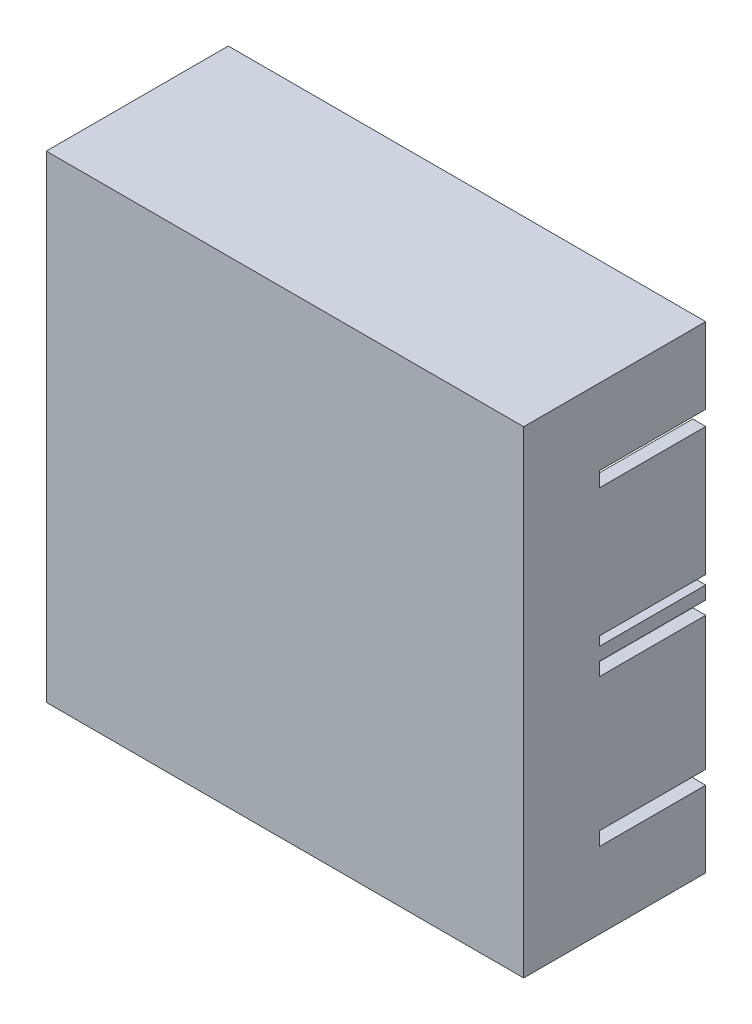
SolidWorks part; units mm, degrees
ref_plane "Front Plane" through (0, 0, 0) normal (0, 0, 1) x (1, 0, 0)
ref_plane "Top Plane" through (0, 0, 0) normal (0, 1, 0) x (1, 0, 0)
ref_plane "Right Plane" through (0, 0, 0) normal (1, 0, 0) x (0, 0, -1)
sketch "Sketch1" plane through (0, 0, 0) normal (0, 0, 1) x (1, 0, 0)
  line L1 (24.5589, 1.4668) -> (46.5589, 1.4668)
  line L2 (24.5589, 1.4668) -> (24.5589, -20.5332)
  line L3 (24.5589, -20.5332) -> (46.5589, -20.5332)
  line L4 (46.5589, 1.4668) -> (46.5589, -20.5332)
  dimension "D1" = 22
  dimension "D2" = 22
extrude "Boss-Extrude1" add sketch "Sketch1" along normal blind 22
sketch "Sketch2" plane through (46.5589, 0, 0) normal (1, 0, 0) x (0, 0, -1)
  line L0 (-22, 1.4668) -> (0, 1.4668) construction
  line L1 (-18.5, -2.0332) -> (-3.5, -2.0332)
  line L2 (-18.5, -2.0332) -> (-18.5, -17.0332)
  line L3 (-18.5, -17.0332) -> (-3.5, -17.0332)
  line L4 (-3.5, -2.0332) -> (-3.5, -17.0332)
  line L5 (0, -20.5332) -> (0, 1.4668) construction
  dimension "D1" = 15
  dimension "D2" = 3.5
  dimension "D3" = 15
  dimension "D4" = 3.5
extrude "Cut-Extrude1" cut sketch "Sketch2" against normal offset from surface (18.5 mm away) 3.5 up to face at (24.5589, -9.5332, 11)
sketch "Sketch4" plane through (0, 0, 3.5) normal (0, 0, 1) x (1, 0, 0)
  line L0 (46.5589, -20.5332) -> (46.5589, 1.4668) construction
  line L1 (46.5589, -4.0418) -> (28.0589, -4.0418)
  line L2 (46.5589, -4.0418) -> (46.5589, -4.6418)
  line L3 (46.5589, -4.6418) -> (28.0589, -4.6418)
  line L4 (28.0589, -4.0418) -> (28.0589, -4.6418)
  line L5 (28.0589, -2.0332) -> (28.0589, -17.0332) construction
  line L6 (46.5589, -9.6418) -> (28.0589, -9.6418)
  line L7 (46.5589, -9.0418) -> (28.0589, -9.0418)
  line L8 (28.0589, -9.0418) -> (28.0589, -9.6418)
  line L9 (46.5589, -9.0418) -> (46.5589, -9.6418)
  line L10 (46.5589, -14.6418) -> (28.0589, -14.6418)
  line L11 (46.5589, -14.0418) -> (28.0589, -14.0418)
  line L12 (28.0589, -14.0418) -> (28.0589, -14.6418)
  line L13 (46.5589, -14.0418) -> (46.5589, -14.6418)
  dimension "D1" = 0.6
  dimension "D2" = 3
extrude "Boss-Extrude2" add sketch "Sketch4" along normal blind 15
sketch "Sketch5" plane through (0, -14.6418, 0) normal (0, -1, 0) x (1, 0, 0)
  line L0 (28.0589, 18.5) -> (46.5589, 18.5) construction
  line L1 (28.0589, 18.5) -> (29.0589, 18.5)
  line L2 (28.0589, 18.5) -> (28.0589, 3.5)
  line L3 (28.0589, 3.5) -> (29.0589, 3.5)
  line L4 (29.0589, 18.5) -> (29.0589, 3.5)
  line L5 (28.0589, 3.5) -> (46.5589, 3.5) construction
  line L6 (28.0589, 18.5) -> (28.0589, 3.5) construction
  dimension "D1" = 1
extrude "Cut-Extrude3" cut sketch "Sketch5" against normal up to surface (10.6 mm away) up to face at (37.3089, -4.0418, 11)
sketch "Sketch3" plane through (46.5589, 0, 0) normal (1, 0, 0) x (0, 0, -1)
  line L0 (-22, 1.4668) -> (0, 1.4668) construction
  line L1 (-13.6119, 1.4668) -> (1.7348, 1.4668)
  line L2 (-13.6119, 1.4668) -> (-13.6119, -21.4019)
  line L3 (-13.6119, -21.4019) -> (1.7348, -21.4019)
  line L4 (1.7348, 1.4668) -> (1.7348, -21.4019)
extrude "Cut-Extrude2" cut sketch "Sketch3" against normal blind 28
sketch "Sketch6" plane through (46.5589, 0, 0) normal (1, 0, 0) x (0, 0, -1)
  line L1 (-18.5, -14.0418) -> (-13.6119, -14.0418)
  line L2 (-18.5, -14.0418) -> (-18.5, -14.6418)
  line L3 (-18.5, -14.6418) -> (-13.6119, -14.6418)
  line L4 (-13.6119, -14.0418) -> (-13.6119, -14.6418)
  line L5 (-18.5, -4.0418) -> (-13.6119, -4.0418)
  line L6 (-18.5, -4.0418) -> (-18.5, -4.6418)
  line L7 (-18.5, -4.6418) -> (-13.6119, -4.6418)
  line L8 (-13.6119, -4.0418) -> (-13.6119, -4.6418)
extrude "Cut-Extrude4" cut sketch "Sketch6" against normal blind 17.5
sketch "Sketch7" plane through (0, 0, 18.5) normal (0, 0, -1) x (-1, 0, 0)
  line L0 (-46.5589, -2.0332) -> (-46.5589, -9.0418) construction
  line L1 (-46.5589, -2.7178) -> (-45.9589, -2.7178)
  line L2 (-46.5589, -2.7178) -> (-46.5589, -8.6254)
  line L3 (-46.5589, -8.6254) -> (-45.9589, -8.6254)
  line L4 (-45.9589, -2.7178) -> (-45.9589, -8.6254)
  line L5 (-46.5589, -9.6418) -> (-46.5589, -17.0332) construction
  line L6 (-46.5589, -10.2514) -> (-45.9589, -10.2514)
  line L7 (-46.5589, -10.2514) -> (-46.5589, -16.4018)
  line L8 (-46.5589, -16.4018) -> (-45.9589, -16.4018)
  line L9 (-45.9589, -10.2514) -> (-45.9589, -16.4018)
  dimension "D1" = 0.6
  dimension "D2" = 0.6
extrude "Boss-Extrude3" add sketch "Sketch7" along normal up to surface (4.8881 mm away) up to face at (36.4339, -9.5332, 13.6119)
